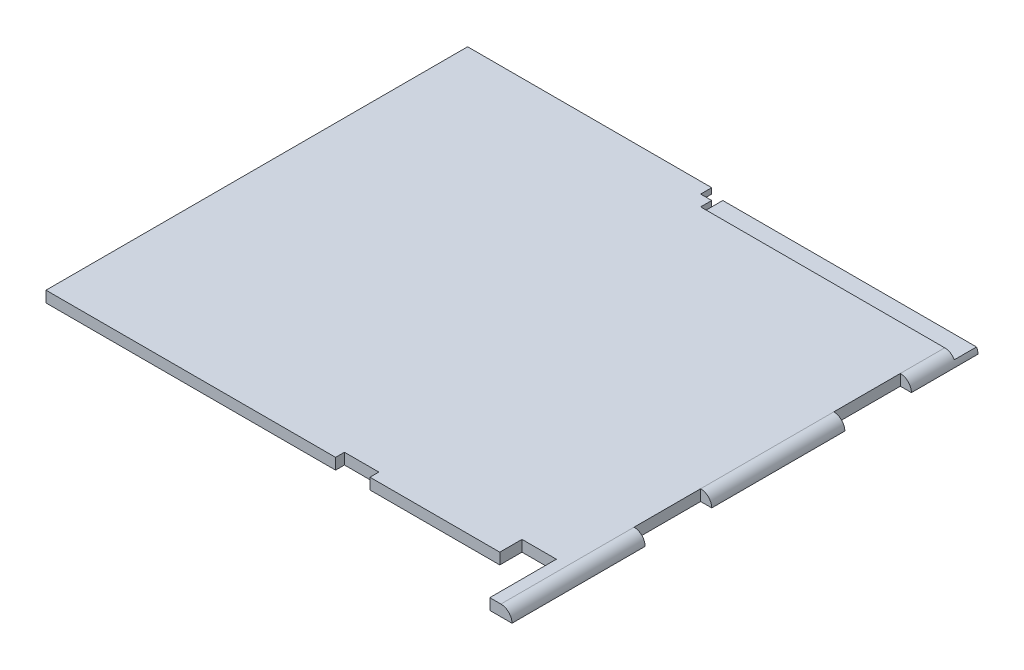
SolidWorks part; units mm, degrees
ref_plane "前基準面" through (0, 0, 0) normal (0, 0, 1) x (1, 0, 0)
ref_plane "上基準面" through (0, 0, 0) normal (0, 1, 0) x (1, 0, 0)
ref_plane "右基準面" through (0, 0, 0) normal (1, 0, 0) x (0, 0, -1)
sketch "草圖1" plane through (0, 0, 0) normal (0, 1, 0) x (1, 0, 0)
  line L0 (-36.2537, 43.5351) -> (203.7463, 43.5351)
  line L1 (203.7463, 43.5351) -> (203.7463, -286.4649)
  line L2 (198.7463, -286.4649) -> (198.7463, -256.4649)
  line L3 (198.7463, -256.4649) -> (183.2463, -256.4649)
  line L4 (183.2463, -256.4649) -> (183.2463, -266.4649)
  line L5 (183.2463, -266.4649) -> (124.7463, -266.4649)
  line L6 (124.7463, -266.4649) -> (124.7463, -262.4649)
  line L7 (124.7463, -262.4649) -> (109.2463, -262.4649)
  line L8 (109.2463, -262.4649) -> (109.2463, -266.4649)
  line L9 (109.2463, -266.4649) -> (-21.2537, -266.4649)
  line L10 (-21.2537, -266.4649) -> (-21.2537, 38.5351)
  line L11 (-21.2537, 38.5351) -> (-36.2537, 38.5351)
  line L12 (-36.2537, 38.5351) -> (-36.2537, 43.5351)
  line L13 (198.7463, -286.4649) -> (203.7463, -286.4649)
  line L15 (203.7463, -286.4649) -> (208.7463, -286.4649)
  line L16 (203.7463, -286.4649) -> (203.7463, -226.4649)
  line L17 (203.7463, -226.4649) -> (208.7463, -226.4649)
  line L18 (208.7463, -286.4649) -> (208.7463, -226.4649)
  line L19 (-36.2537, 43.5351) -> (-6.2537, 43.5351)
  line L20 (-36.2537, 43.5351) -> (-36.2537, 48.5351)
  line L21 (-36.2537, 48.5351) -> (-6.2537, 48.5351)
  line L22 (-6.2537, 43.5351) -> (-6.2537, 48.5351)
  line L23 (203.7463, 43.5351) -> (173.7463, 43.5351)
  line L24 (203.7463, 43.5351) -> (203.7463, 48.5351)
  line L25 (203.7463, 48.5351) -> (173.7463, 48.5351)
  line L26 (173.7463, 43.5351) -> (173.7463, 48.5351)
  line L27 (203.7463, 43.5351) -> (208.7463, 43.5351)
  line L28 (203.7463, 43.5351) -> (203.7463, -16.4649)
  line L29 (203.7463, -16.4649) -> (208.7463, -16.4649)
  line L30 (208.7463, 43.5351) -> (208.7463, -16.4649)
  line L31 (83.7463, 43.5351) -> (98.7463, 43.5351)
  line L32 (83.7463, 43.5351) -> (83.7463, 48.5351)
  line L33 (83.7463, 48.5351) -> (98.7463, 48.5351)
  line L34 (98.7463, 43.5351) -> (98.7463, 48.5351)
  line L35 (83.7463, 43.5351) -> (68.7463, 43.5351)
  line L36 (83.7463, 43.5351) -> (83.7463, 48.5351)
  line L37 (83.7463, 48.5351) -> (68.7463, 48.5351)
  line L38 (68.7463, 43.5351) -> (68.7463, 48.5351)
  line L39 (203.7463, -46.4649) -> (208.7463, -46.4649)
  line L40 (203.7463, -46.4649) -> (203.7463, -106.4649)
  line L41 (203.7463, -106.4649) -> (208.7463, -106.4649)
  line L42 (208.7463, -46.4649) -> (208.7463, -106.4649)
  line L43 (203.7463, -136.4649) -> (208.7463, -136.4649)
  line L44 (203.7463, -136.4649) -> (203.7463, -196.4649)
  line L45 (203.7463, -196.4649) -> (208.7463, -196.4649)
  line L46 (208.7463, -136.4649) -> (208.7463, -196.4649)
  dimension "D3" = 5
  dimension "D1" = 240
  dimension "D2" = 330
  dimension "D4" = 15
  dimension "D5" = 130.5
  dimension "D6" = 4
  dimension "D7" = 4
  dimension "D8" = 15.5
  dimension "D9" = 58.5
  dimension "D10" = 10
  dimension "D11" = 15.5
  dimension "D12" = 30
  dimension "D13" = 5
  dimension "D14" = 60
  dimension "D15" = 5
  dimension "D16" = 5
  dimension "D17" = 30
  dimension "D18" = 5
  dimension "D19" = 30
  dimension "D20" = 60
  dimension "D21" = 5
  dimension "D22" = 5
  dimension "D23" = 15
  dimension "D24" = 5
  dimension "D25" = 15
  dimension "D26" = 60
  dimension "D27" = 5
  dimension "D28" = 30
  dimension "D29" = 60
  dimension "D30" = 5
  dimension "D31" = 30
  dimension "D32" = 30
extrude "填料-伸長1" add sketch "草圖1" along normal blind 5 contours L2 L13 L1 L0 L12 L11 L10 L9 L8 L7 L6 L5 L4 L3 | L15 L18 L17 L1 | L30 L27 L1 L29 | L26 L0 L24 L25 | L0 L22 L21 L20 | L32 L33 L34 L31 | L36 L37 L38 L35 | L46 L45 L44 L43 | L42 L41 L40 L39 region at (-21.2537, 0, -46.0351) region at (91.0303, 0, 111.0679) region at (188.7463, 0, -46.0351) region at (206.2463, 0, -13.5351) region at (206.2463, 0, 256.4649)
fillet "圓角1" radius 5 4 edges at (208.7463, 5, -13.5351) (208.7463, 5, 76.4649) (208.7463, 5, 166.4649) (208.7463, 5, 256.4649)
sketch "草圖2" plane through (0, 5, 0) normal (0, 1, 0) x (1, 0, 0)
  line L1 (-36.2537, 48.5351) -> (208.7463, 48.5351)
  line L2 (-36.2537, 48.5351) -> (-36.2537, -76.4649)
  line L3 (-36.2537, -76.4649) -> (208.7463, -76.4649)
  line L4 (208.7463, 48.5351) -> (208.7463, -76.4649)
  dimension "D1" = 125
extrude "除料-伸長1" cut sketch "草圖2" against normal blind 5
sketch "草圖3" plane through (0, 0, 76.4649) normal (0, 0, -1) x (-1, 0, 0)
  line L1 (21.2537, 0) -> (-88.7463, 0)
  line L2 (21.2537, 0) -> (21.2537, 2.5)
  line L3 (21.2537, 2.5) -> (-88.7463, 2.5)
  line L4 (-88.7463, 0) -> (-88.7463, 2.5)
  line L5 (-93.7463, 2.5) -> (-208.7463, 2.5)
  line L6 (-93.7463, 2.5) -> (-93.7463, 5)
  line L7 (-93.7463, 5) -> (-208.7463, 5)
  line L8 (-208.7463, 2.5) -> (-208.7463, 5)
  point P9 (-93.7463, 3.75)
  dimension "D1" = 2.5
  dimension "D2" = 110
  dimension "D3" = 2.5
  dimension "D4" = 115
  dimension "D5" = 5
extrude "除料-伸長2" cut sketch "草圖3" against normal blind 10
sketch "草圖4" plane through (0, 0, 76.4649) normal (0, 0, -1) x (-1, 0, 0)
  line L1 (-93.7463, 5) -> (-88.7463, 5)
  line L2 (-93.7463, 5) -> (-93.7463, 0)
  line L3 (-93.7463, 0) -> (-88.7463, 0)
  line L4 (-88.7463, 5) -> (-88.7463, 0)
extrude "除料-伸長3" cut sketch "草圖4" against normal blind 5
